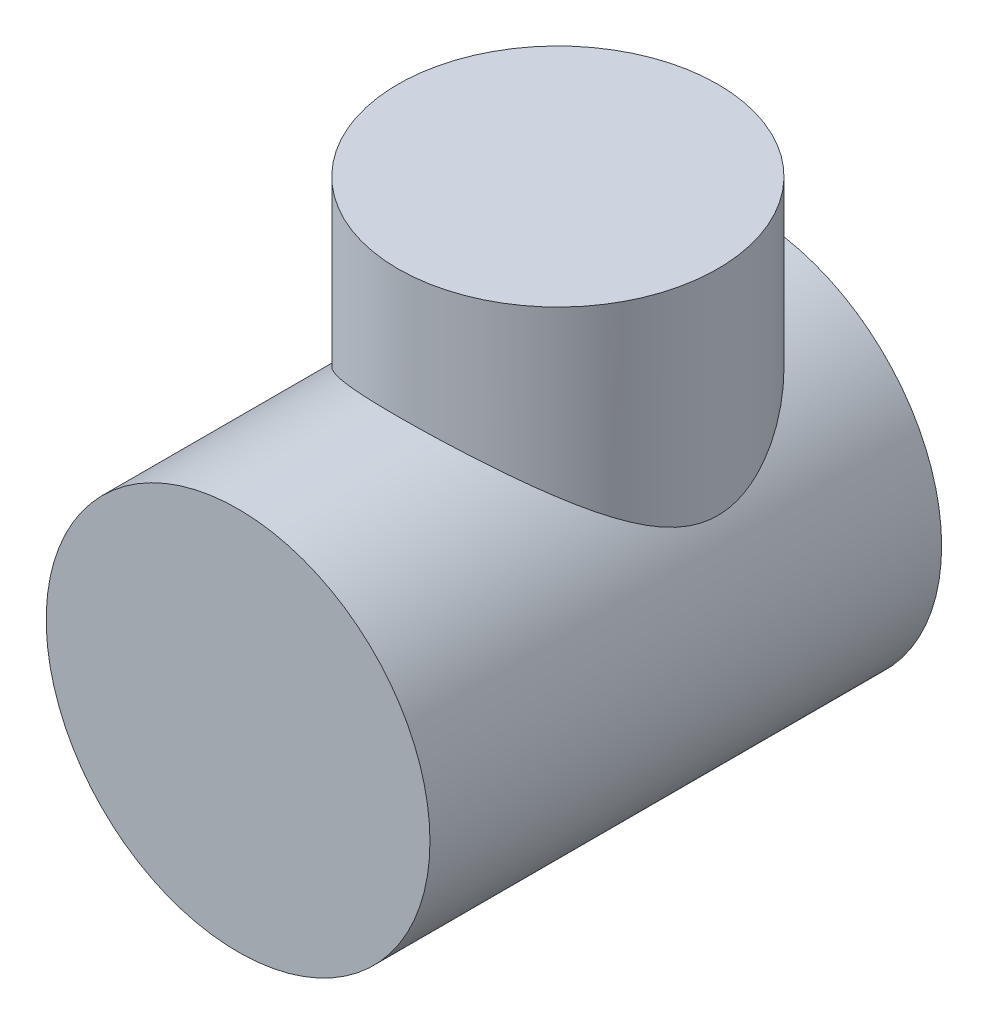
SolidWorks part; units mm, degrees
ref_plane "前视基准面" through (0, 0, 0) normal (0, 0, 1) x (1, 0, 0)
ref_plane "上视基准面" through (0, 0, 0) normal (0, 1, 0) x (1, 0, 0)
ref_plane "右视基准面" through (0, 0, 0) normal (1, 0, 0) x (0, 0, -1)
sketch "草图1" plane through (0, 0, 0) normal (0, 0, 1) x (1, 0, 0)
  circle A0 centre (0, 0) radius 300
extrude "凸台-拉伸1" add sketch "草图1" along normal blind 800
sketch "草图2" plane through (0, 0, 0) normal (0, 1, 0) x (1, 0, 0)
  circle A0 centre (0, -300) radius 250
  dimension "D1" = 300
extrude "凸台-拉伸2" add sketch "草图2" along normal blind 500
ref_axis "基准轴1" through (0, 500, 300) along (0, -1, 0)
ref_axis "基准轴2" through (0, 0, 800) along (0, 0, -1)
ref_point "点2"
